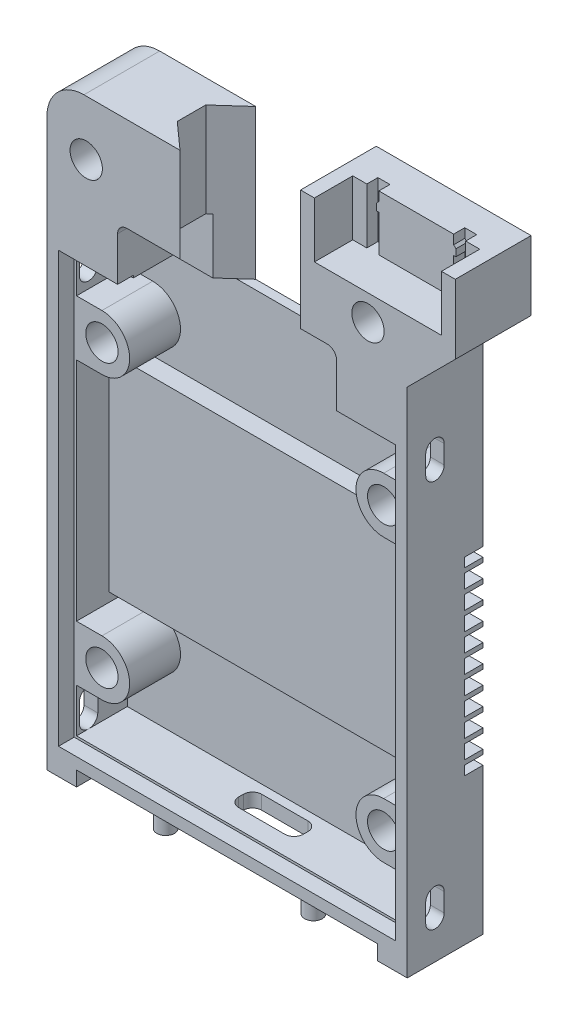
SolidWorks part; units mm, degrees
ref_plane "Front Plane" through (0, 0, 0) normal (0, 0, 1) x (1, 0, 0)
ref_plane "Top Plane" through (0, 0, 0) normal (0, 1, 0) x (1, 0, 0)
ref_plane "Right Plane" through (0, 0, 0) normal (1, 0, 0) x (0, 0, -1)
sketch "Sketch1" plane through (0, 0, 0) normal (0, 0, 1) x (1, 0, 0)
  line L0 (15.25, -20.35) -> (18, -20.35)
  line L1 (-19.5, -32.6) -> (19.5, -32.6)
  line L2 (-19.5, -32.6) -> (-19.5, 31.1)
  line L3 (-19.5, 31.1) -> (19.5, 31.1)
  line L4 (19.5, -32.6) -> (19.5, 31.1)
  line L5 (-15.25, -20.35) -> (-18, -20.35)
  line L6 (15.25, -26.35) -> (18, -26.35)
  line L7 (6.95, 31.1) -> (-15.5, 31.1) construction
  line L8 (-18, -31.1) -> (-18, 29.6)
  line L9 (-18, 29.6) -> (18, 29.6)
  line L10 (18, -31.1) -> (18, 29.6)
  line L11 (-18, -31.1) -> (18, -31.1)
  line L12 (-18, 14.9) -> (18, 14.9)
  line L13 (7.85, 14.9) -> (-4.95, 14.9) construction
  line L14 (-15.25, 4.15) -> (-18, 4.15)
  line L15 (-15.25, 10.15) -> (-18, 10.15)
  line L16 (15.25, 10.15) -> (18, 10.15)
  line L17 (15.25, 4.15) -> (18, 4.15)
  line L18 (-15.25, -26.35) -> (-18, -26.35)
  line L19 (19.5, -34.2) -> (19.5, -18.35) construction
  line L20 (-19.5, -34.2) -> (-19.5, -18.35) construction
  line L21 (15.3, -32.6) -> (-15.3, -32.6) construction
  line L22 (0, 31.1) -> (0, -32.6) construction
  line L23 (9.45, 26.9) -> (24.7, 26.9)
  line L24 (9.45, 26.9) -> (9.45, 33.9)
  line L25 (9.45, 33.9) -> (24.7, 33.9)
  line L26 (24.7, 26.9) -> (24.7, 33.9)
  line L27 (18, 29.6) -> (19.5, 31.1) construction
  line L28 (18.75, 30.35) -> (0, 30.35) construction
  line L29 (9.45, 26.9) -> (7.95, 26.9) construction
  line L30 (-7.95, 31.1) -> (7.95, 31.1)
  line L31 (-7.95, 31.1) -> (-7.95, 29.6)
  line L32 (-7.95, 29.6) -> (7.95, 29.6)
  line L33 (7.95, 31.1) -> (7.95, 29.6)
  line L34 (-7.95, 31.1) -> (7.95, 29.6) construction
  line L35 (-7.95, 29.6) -> (7.95, 31.1) construction
  line L36 (7.95, 26.9) -> (7.95, 29.6) construction
  line L37 (18, 29.6) -> (19.5, 29.6) construction
  line L38 (24.7, 26.4) -> (19.5, 21.2)
  line L39 (9.45, 33.9) -> (7.95, 33.9)
  line L40 (23.2, 33.9) -> (23.2, 26.9)
  line L41 (7.95, 33.9) -> (7.95, 31.1)
  line L42 (24.7, 30.4) -> (23.2, 30.4) construction
  line L43 (24.7, 26.9) -> (19.5, 26.9)
  line L44 (24.7, 26.9) -> (24.7, 26.4)
  line L45 (24.7, 26.4) -> (19.5, 26.4)
  line L46 (19.5, 26.9) -> (19.5, 26.4)
  circle A0 centre (15.25, -23.35) radius 1.75
  arc A1 (-15.5, 31.1) -> (-19.5, 27.1) centre (-15.5, 27.1) ccw construction
  circle A2 centre (15.25, -23.35) radius 3
  arc A3 (-15.5, 31.1) -> (-19.5, 27.1) centre (-15.5, 27.1) ccw
  arc A4 (-15.5, 29.6) -> (-18, 27.1) centre (-15.5, 27.1) ccw
  circle A6 centre (-15.25, -23.35) radius 1.75
  circle A7 centre (-15.25, -23.35) radius 1.75
  circle A8 centre (-15.25, 7.15) radius 1.75
  circle A9 centre (15.25, 7.15) radius 1.75
  circle A10 centre (15.25, 25.15) radius 1.75
  circle A11 centre (-15.25, 25.15) radius 1.75
  circle A12 centre (-15.25, -23.35) radius 3
  circle A13 centre (-15.25, -23.35) radius 3
  circle A14 centre (15.25, 7.15) radius 3
  circle A15 centre (-15.25, 7.15) radius 3
  dimension "D2" = 1.5
  dimension "D4" = 6
  dimension "D3" = 3.5
  dimension "D5" = 13.75
  dimension "D6" = 15.9
  dimension "D7" = 7
  dimension "D8" = 45
  dimension "D9" = 0.5
  dimension "D1" = 1.5
extrude "Base shape" add sketch "Sketch1" along normal up to surface (8.2 mm away) contours A15 L8 L9 L31 L3 A3 L2 L1 L4 L23 L10 A14 A2 L11 A12 | A12 L8 L18 | A12 L8 A6 | L8 A12 | A12 L5 L8 | A15 L8 L14 | A15 L8 A8 | L8 A15 | A15 L15 L8 | L23 A10 L24 L9 A4 L8 L12 L10 A11 | A4 L9 L8 | L33 L3 L31 L9 | L3 L33 L9 L24 | L24 L9 L10 L23 L4 L3 | L24 L23 L10 L9 | A14 L10 L16 | L10 A14 A9 | A14 L17 L10 | L10 A14 | L10 A2 L6 | A2 L10 A0 | L0 A2 L10 | A2 L10 | L40 L25 L24 L3 L4 L23 | L25 L40 L23 L26 | L38 L45 L4 | L45 L44 L23 L4 | L39 L41 L3 L24 region at (16.8481, -20.9099, 0) region at (17.3601, -20.8437, 0) region at (18.7469, -8.1, 0) region at (17.3601, -25.8563, 0) region at (18.1004, -23.35, 0) region at (17.3601, 4.6437, 0) region at (16.8481, 4.7099, 0) region at (18.1004, 7.15, 0) region at (17.3601, 9.6563, 0) region at (-17.3601, -25.8563, 0) region at (-0.6044, 21.831, 0) region at (-18.1004, -23.35, 0) region at (-17.9169, -23.35, 0) region at (13.725, 28.25, 0) region at (15.3803, 29.9053, 0) region at (-17.3601, -20.8437, 0) region at (22.1, 26.65, 0) region at (17.77, 31.4935, 0) region at (-17.3601, 9.6563, 0) region at (-17.4416, 29.0416, 0) region at (8.7, 30.35, 0) region at (21.2333, 24.6667, 0) region at (23.95, 30.4, 0) region at (-16.8481, 9.5901, 0) region at (-18.1004, 7.15, 0) region at (-17.3601, 4.6437, 0) region at (0, 30.35, 0) region at (8.7, 32.5, 0)
sketch "Sketch3" plane through (19.5, 0, 0) normal (1, 0, 0) x (0, 0, -1)
  line L1 (0, -18.35) -> (-2, -18.35)
  line L2 (0, -18.35) -> (0, 2.15)
  line L3 (0, 2.15) -> (-2, 2.15)
  line L4 (-2, -18.35) -> (-2, 2.15)
  line L5 (0, -18.35) -> (1.75, -18.35) construction
  line L6 (0, 2.15) -> (1.75, 2.15) construction
  line L7 (0, -32.6) -> (0, 21.2) construction
  dimension "D1" = 2
extrude "Strap cut" cut sketch "Sketch3" against normal through all
sketch "Sketch4" plane through (0, 31.1, 0) normal (0, 1, 0) x (1, 0, 0)
  line L2 (7.95, 0) -> (-5.0998, 0)
  line L4 (-15.5, 0) -> (7.95, 0) construction
  line L5 (-15.5, -8.2) -> (7.95, -8.2) construction
  line L6 (7.95, -8.2) -> (-5.0998, -8.2)
  line L12 (7.95, -8.3) -> (7.95, 0.1)
  line L13 (7.95, 0.1) -> (-4.9883, 0.1)
  line L14 (-4.9883, 0.1) -> (-7.95, -2.5553)
  line L15 (-7.95, -2.5553) -> (-7.95, -5.6447)
  line L16 (-7.95, -5.6447) -> (-4.9883, -8.3)
  line L17 (-4.9883, -8.3) -> (7.95, -8.3)
  line L18 (7.95, -8.3) -> (7.95, 0.1)
  line L19 (7.95, 0.1) -> (-4.9883, 0.1)
  line L20 (-4.9883, 0.1) -> (-7.95, -2.5553)
  line L21 (-7.95, -2.5553) -> (-7.95, -5.6447)
  line L22 (-7.95, -5.6447) -> (-4.9883, -8.3)
  line L23 (-4.9883, -8.3) -> (7.95, -8.3)
  dimension "D1" = 0.1
extrude "XT60 cut" cut sketch "Sketch4" against normal up to next contours L21 L22 L18 L20 region at (0.4142, 31.1, 4.1)
sketch "Sketch5" plane through (19.5, 0, 0) normal (1, 0, 0) x (0, 0, -1)
  line L1 (-8.2, -32.6) -> (-8.2, 21.2) construction
  line L2 (-6.2, -31.1) -> (-4.2, -31.1)
  line L3 (-6.2, -31.1) -> (-6.2, -27.1)
  line L4 (-6.2, -27.1) -> (-4.2, -27.1)
  line L5 (-4.2, -31.1) -> (-4.2, -27.1)
  line L6 (-8.2, -31.1) -> (0, -31.1) construction
  line L7 (-8.2, 14.9) -> (0, 14.9) construction
  line L8 (-6.2, 14.9) -> (-4.2, 14.9)
  line L9 (-6.2, 14.9) -> (-6.2, 10.9)
  line L10 (-6.2, 10.9) -> (-4.2, 10.9)
  line L11 (-4.2, 14.9) -> (-4.2, 10.9)
  line L14 (-5.2, -27.1) -> (-5.2, -31.1) construction
  line L15 (-5.2, 14.9) -> (-5.2, 10.9) construction
  circle A0 centre (-5.2, -28.1) radius 1
  circle A1 centre (-5.2, -30.1) radius 1
  circle A2 centre (-5.2, 13.9) radius 1
  circle A3 centre (-5.2, 11.9) radius 1
  point P20 (-5.2, -29.1)
  point P31 (-5.2, 12.9)
  dimension "D3" = 4
  dimension "D1" = 2
  dimension "D2" = 2
extrude "Power wires cut" cut sketch "Sketch5" against normal through all contours A2 | A3 | A3 A2 L9 | A3 L11 A2 | A1 | A0 | A1 L5 A0 | A1 A0 L3 region at (19.5, -30.1, 5.2) region at (19.5, -29.1, 5.9766) region at (19.5, -29.1, 4.4234) region at (19.5, -28.1, 5.2) region at (19.5, 13.9, 5.2) region at (19.5, 12.9, 5.9766) region at (19.5, 12.9, 4.4234) region at (19.5, 11.9, 5.2)
sketch "Sketch6" plane through (0, 0, 8.2) normal (0, 0, 1) x (1, 0, 0)
  line L0 (9.15, 14.9) -> (10.85, 14.9) construction
  line L1 (-11.85, 19.9) -> (11.85, 19.9)
  line L2 (-11.85, 19.9) -> (-11.85, 14.9)
  line L3 (-11.85, 14.9) -> (11.85, 14.9)
  line L4 (11.85, 19.9) -> (11.85, 14.9)
  line L5 (-10.85, 20.9) -> (10.85, 20.9)
  arc A0 (11.85, 19.9) -> (10.85, 20.9) centre (10.85, 19.9) ccw construction
  arc A1 (-10.85, 20.9) -> (-11.85, 19.9) centre (-10.85, 19.9) ccw construction
  arc A2 (11.85, 19.9) -> (10.85, 20.9) centre (10.85, 19.9) ccw
  arc A3 (-10.85, 20.9) -> (-11.85, 19.9) centre (-10.85, 19.9) ccw
  line M1 (7.95, 33.9) -> (7.95, 14.9)
  line M15 (-5.0998, 14.9) -> (-5.0998, 31.1)
  line M118 (7.95, 14.9) -> (18, 14.9)
  line M134 (-18, 14.9) -> (-5.0998, 14.9)
extrude "IO wires cut" cut sketch "Sketch6" against normal blind 6 contours L5 A3 L1 M15 | L1 L2 M134 M15 | L5 L1 M15 M1 | L3 L1 M15 M1 | L1 A2 L5 M1 | L4 L1 M1 M118 region at (-8.3714, 20.3909, 8.2) region at (-8.4749, 17.4, 8.2) region at (1.4251, 20.4, 8.2) region at (1.4251, 17.4, 8.2) region at (9.7995, 20.3839, 8.2) region at (9.9, 17.4, 8.2)
sketch "Sketch7" plane through (-18, 0, 0) normal (1, 0, 0) x (0, 0, -1)
  line L6 (0, -18.35) -> (0, -20.35)
  line L7 (-2, -18.35) -> (0, -18.35)
  line L8 (-2, 2.15) -> (-2, -18.35)
  line L9 (0, 2.15) -> (-2, 2.15)
  line L12 (0, 3.15) -> (-3, 3.15)
  line L13 (-3, 3.15) -> (-3, -19.35)
  line L14 (-3, -19.35) -> (-1, -19.35)
  line L15 (-1, -19.35) -> (-1, -20.35)
  line L16 (-1, -20.35) -> (0, -20.35)
  line L17 (0, 3.15) -> (-1, 3.15)
  line L19 (0, -31.1) -> (-1, -31.1)
  line L22 (0, -31.1) -> (0, -20.35)
  line L23 (0, -20.35) -> (-1, -20.35)
  line L24 (-1, -31.1) -> (-1, -20.35)
  line L25 (0, 3.15) -> (0, 14.9)
  line L26 (0, 14.9) -> (-1, 14.9)
  line L27 (-1, 3.15) -> (-1, 14.9)
  line L28 (-5.2, 14.9) -> (0, 14.9) construction
  line L31 (0, -20.35) -> (0, -18.35) construction
  line L32 (0, 2.15) -> (-2, 2.15) construction
  line M48 (0, -20.35) -> (0, -18.35)
  line M49 (0, -18.35) -> (-2, -18.35)
  line M50 (-2, -18.35) -> (-2, 2.15)
  line M51 (-2, 2.15) -> (0, 2.15)
  line M52 (0, 2.15) -> (0, 4.15)
  line M53 (0, 4.15) -> (-8.2, 4.15)
  line M55 (-8.2, -20.35) -> (0, -20.35)
  dimension "D1" = 1
extrude "Bottom" add sketch "Sketch7" along normal up to surface (36 mm away) contours L27 L25 L26 M53 | L27 L12 M52 M53 | L14 L15 L12 L13 M55 M48 M49 M50 M51 M52 | L24 L19 L22 M55 region at (-18, -8.5273, 2.2091) region at (-18, -25.725, 0.5) region at (-18, 3.65, 0.5) region at (-18, 9.525, 0.5) up to face at (18, -8.1, 2.55)
sketch "Sketch9" plane through (0, 0, 0) normal (0, 0, -1) x (-1, 0, 0)
  circle A0 centre (15.25, -23.35) radius 1.75 construction
  circle A1 centre (-15.25, 7.15) radius 1.75 construction
  circle A2 centre (15.25, 7.15) radius 1.75 construction
  circle A3 centre (15.25, -23.35) radius 1.75 construction
  circle A4 centre (15.25, -23.35) radius 1.75
  circle A5 centre (-15.25, 7.15) radius 1.75
  circle A6 centre (15.25, 7.15) radius 1.75
  circle A7 centre (15.25, -23.35) radius 1.75
  circle A8 centre (-15.25, -23.35) radius 1.75 construction
  circle A9 centre (-15.25, -23.35) radius 1.75
extrude "Bottom holes" cut sketch "Sketch9" against normal up to next contours A5 | A6 | A4 | A9 region at (-15.25, -23.35, 0) region at (15.25, 7.15, 0) region at (-15.25, 7.15, 0) region at (15.25, -23.35, 0)
sketch "Sketch8" plane through (0, 0, 8.2) normal (0, 0, 1) x (1, 0, 0)
  line L0 (-6.2152, 14.9) -> (-18, 14.9) construction
  line L1 (-18.25, 15.15) -> (18.25, 15.15)
  line L2 (-18.25, 15.15) -> (-18.25, -31.35)
  line L3 (-18.25, -31.35) -> (18.25, -31.35)
  line L4 (18.25, 15.15) -> (18.25, -31.35)
  line L5 (-18, 14.9) -> (-18.25, 14.9) construction
  line L6 (-18, 14.9) -> (-18, 15.15) construction
  line L7 (18, 14.9) -> (18.25, 14.9) construction
  line L8 (-18, -31.1) -> (-18, -31.35) construction
  dimension "D1" = 0.25
extrude "PCB cut" cut sketch "Sketch8" against normal blind 1.7
sketch "Sketch11" plane through (0, -32.6, 0) normal (0, -1, 0) x (1, 0, 0)
  line L0 (19.5, 8.2) -> (19.5, 0) construction
  line L1 (-19.5, 8.2) -> (19.5, 8.2)
  line L2 (-19.5, 8.2) -> (-19.5, -1.8)
  line L3 (-19.5, -1.8) -> (19.5, -1.8)
  line L4 (19.5, 8.2) -> (19.5, -1.8)
  line L5 (-19.5, 3.2) -> (19.5, 3.2) construction
  line L6 (0, -1.8) -> (0, 8.2) construction
  line L8 (-2.5, 4.45) -> (2.5, 4.45)
  line L9 (-3.5, 3.45) -> (-3.5, 2.95)
  line L10 (-2.5, 1.95) -> (2.5, 1.95)
  line L11 (3.5, 3.45) -> (3.5, 2.95)
  line L12 (-3.5, 4.45) -> (3.5, 1.95) construction
  line L13 (-3.5, 1.95) -> (3.5, 4.45) construction
  arc A0 (2.5, 4.45) -> (3.5, 3.45) centre (2.5, 3.45) cw
  arc A1 (2.5, 1.95) -> (3.5, 2.95) centre (2.5, 2.95) ccw
  arc A2 (-3.5, 2.95) -> (-2.5, 1.95) centre (-2.5, 2.95) ccw
  arc A3 (-2.5, 4.45) -> (-3.5, 3.45) centre (-2.5, 3.45) ccw
  point P11 (0, 3.2)
  dimension "D4" = 1
  dimension "D1" = 10
  dimension "D2" = 7
  dimension "D3" = 2.5
extrude "Ledbar wires cut" cut sketch "Sketch11" against normal up to next contours L8 A3 L9 A2 L10 A1 L11 A0 region at (0, -32.6, 3.2)
sketch "Sketch13" plane through (0, -32.6, 0) normal (0, -1, 0) x (1, 0, 0)
  line L0 (-19.5, 8.2) -> (19.5, 8.2) construction
  line L1 (19.5, 0) -> (16.3, 0)
  line L2 (19.5, 0) -> (19.5, 8.2)
  line L3 (19.5, 8.2) -> (16.3, 8.2)
  line L4 (16.3, 0) -> (16.3, 8.2)
  line L5 (16.1, -1.8) -> (16.1, 8.2) construction
  line L6 (0, 8.2) -> (0, 0) construction
  line L7 (-19.5, 0) -> (-16.3, 0)
  line L8 (-19.5, 0) -> (-19.5, 8.2)
  line L9 (-19.5, 8.2) -> (-16.3, 8.2)
  line L10 (-16.3, 0) -> (-16.3, 8.2)
  dimension "D1" = 0.2
extrude "Ledbar sides" add sketch "Sketch13" along normal blind 1.6
sketch "Sketch14" plane through (0, -32.6, 0) normal (0, -1, 0) x (1, 0, 0)
  circle A0 centre (8, 6.85) radius 0.95
  circle A1 centre (-8, 6.85) radius 0.95
  dimension "D1" = 1.9
extrude "Ledbar mounts" add sketch "Sketch14" along normal blind 2
sketch "Sketch16" plane through (0, 33.9, 0) normal (0, 1, 0) x (1, 0, 0)
  line L0 (7.95, -6.125) -> (24.7, -6.125) construction
  line L1 (7.95, -8.2) -> (24.7, -8.2) construction
  line L2 (21.675, -2.85) -> (20.375, -2.85)
  line L3 (20.375, -4.05) -> (20.375, -2.85)
  line L4 (9.45, -4.05) -> (23.2, -4.05)
  line L5 (9.45, -4.05) -> (9.45, -8.2)
  line L6 (9.45, -8.2) -> (23.2, -8.2)
  line L7 (23.2, -4.05) -> (23.2, -8.2)
  line L8 (9.45, -4.05) -> (23.2, -8.2) construction
  line L9 (9.45, -8.2) -> (23.2, -4.05) construction
  line L10 (24.7, -8.2) -> (24.7, 0) construction
  line L11 (7.95, -8.2) -> (7.95, 0) construction
  line L12 (16.325, -8.2) -> (16.325, -4.05) construction
  line L13 (11.625, -2.85) -> (11.625, -4.05) construction
  line L14 (10.975, -4.05) -> (12.275, -4.05)
  line L15 (10.975, -4.05) -> (10.975, -2.85)
  line L16 (10.975, -2.85) -> (12.275, -2.85)
  line L17 (12.275, -4.05) -> (12.275, -2.85)
  line L18 (10.975, -2.85) -> (10.975, -8.2) construction
  line L19 (21.675, -4.05) -> (21.675, -2.85)
  point P6 (16.325, -6.125)
  dimension "D1" = 13.75
  dimension "D2" = 4.15
  dimension "D3" = 1.3
  dimension "D4" = 1.2
  dimension "D5" = 4.7
extrude "Balance plug cut" cut sketch "Sketch16" against normal blind 6 contours L7 L4 L5 L6 | L4 L17 L16 L15 | L4 L19 L2 L3 region at (21.025, 33.9, 3.45) region at (16.325, 33.9, 6.125) region at (11.625, 33.9, 3.45)
sketch "Sketch17" plane through (0, 0, 2.85) normal (0, 0, 1) x (1, 0, 0)
  line L0 (16.325, 33.9) -> (16.325, 27.9) construction
  line L1 (12.275, 33.9) -> (20.375, 33.9) construction
  line L2 (12.275, 27.9) -> (20.375, 27.9) construction
  line L3 (12.275, 27.9) -> (12.275, 33.9) construction
  line L4 (12.025, 32.9) -> (20.625, 32.9)
  line L5 (12.025, 32.9) -> (12.025, 31.9)
  line L6 (12.025, 31.9) -> (20.625, 31.9)
  line L7 (20.625, 32.9) -> (20.625, 31.9)
  line L8 (12.025, 32.9) -> (20.625, 31.9) construction
  line L9 (12.025, 31.9) -> (20.625, 32.9) construction
  line L10 (12.025, 32.65) -> (12.275, 32.9)
  line L11 (20.625, 32.65) -> (20.375, 32.9)
  point P6 (16.325, 32.4)
  line M7 (20.375, 33.9) -> (20.375, 27.9)
  dimension "D1" = 0.25
  dimension "D2" = 1
  dimension "D3" = 1
  dimension "D4" = 45
extrude "Balance plug locks" add sketch "Sketch17" along normal up to surface (1.2 mm away) contours L10 L5 L6 L4 M7 | L7 L11 L6 M7 region at (16.2154, 32.3984, 2.85) region at (20.494, 32.3405, 2.85) up to face at (16.325, 30.9, 4.05)
sketch "Sketch10" plane through (0, 0, 2) normal (0, 0, -1) x (-1, 0, 0)
  line L0 (0, 2.15) -> (0, -18.35) construction
  line L1 (19.5, 2.15) -> (-19.5, 2.15) construction
  line L2 (19.5, -18.35) -> (-19.5, -18.35) construction
  line L3 (19.5, 2.15) -> (19.5, -18.35) construction
  line L4 (-19.5, 1.15) -> (19.5, 1.15)
  line L5 (-19.5, 1.15) -> (-19.5, 0.65)
  line L6 (-19.5, 0.65) -> (19.5, 0.65)
  line L7 (19.5, 1.15) -> (19.5, 0.65)
  line L8 (-19.5, 1.15) -> (19.5, 0.65) construction
  line L9 (-19.5, 0.65) -> (19.5, 1.15) construction
  line L10 (-19.5, 2.15) -> (19.5, 2.15) construction
  line L11 (-19.5, -1.35) -> (19.5, -1.35)
  line L12 (19.5, -0.85) -> (19.5, -1.35)
  line L13 (-19.5, -0.85) -> (19.5, -0.85)
  line L14 (-19.5, -0.85) -> (-19.5, -1.35)
  line L15 (-19.5, -3.35) -> (19.5, -3.35)
  line L16 (19.5, -2.85) -> (19.5, -3.35)
  line L17 (-19.5, -2.85) -> (19.5, -2.85)
  line L18 (-19.5, -2.85) -> (-19.5, -3.35)
  line L19 (-19.5, -5.35) -> (19.5, -5.35)
  line L20 (19.5, -4.85) -> (19.5, -5.35)
  line L21 (-19.5, -4.85) -> (19.5, -4.85)
  line L22 (-19.5, -4.85) -> (-19.5, -5.35)
  line L23 (-19.5, -7.35) -> (19.5, -7.35)
  line L24 (19.5, -6.85) -> (19.5, -7.35)
  line L25 (-19.5, -6.85) -> (19.5, -6.85)
  line L26 (-19.5, -6.85) -> (-19.5, -7.35)
  line L27 (-19.5, -9.35) -> (19.5, -9.35)
  line L28 (19.5, -8.85) -> (19.5, -9.35)
  line L29 (-19.5, -8.85) -> (19.5, -8.85)
  line L30 (-19.5, -8.85) -> (-19.5, -9.35)
  line L31 (-19.5, -11.35) -> (19.5, -11.35)
  line L32 (19.5, -10.85) -> (19.5, -11.35)
  line L33 (-19.5, -10.85) -> (19.5, -10.85)
  line L34 (-19.5, -10.85) -> (-19.5, -11.35)
  line L35 (-19.5, -13.35) -> (19.5, -13.35)
  line L36 (19.5, -12.85) -> (19.5, -13.35)
  line L37 (-19.5, -12.85) -> (19.5, -12.85)
  line L38 (-19.5, -12.85) -> (-19.5, -13.35)
  line L39 (-19.5, -15.35) -> (19.5, -15.35)
  line L40 (19.5, -14.85) -> (19.5, -15.35)
  line L41 (-19.5, -14.85) -> (19.5, -14.85)
  line L42 (-19.5, -14.85) -> (-19.5, -15.35)
  line L43 (-19.5, -17.35) -> (19.5, -17.35)
  line L44 (19.5, -16.85) -> (19.5, -17.35)
  line L45 (-19.5, -16.85) -> (19.5, -16.85)
  line L46 (-19.5, -16.85) -> (-19.5, -17.35)
  point P6 (0, 0.9)
  dimension "D1" = 1
  dimension "D2" = 0.5
  dimension "D4" = 2
  dimension "D3" = 10
extrude "3D print ribs" add sketch "Sketch10" along normal up to surface (2 mm away) up to face at (-17, 7.15, 0)
sketch "Sketch15" plane through (0, 0, 0) normal (0, 0, -1) x (-1, 0, 0)
  line L0 (-8, -34.6) -> (-8, -32.6) construction
  line L1 (-8.95, -34.6) -> (-7.05, -34.6) construction
  line L2 (-8.95, -32.6) -> (-7.05, -32.6) construction
  line L3 (0, -32.6) -> (0, 14.9) construction
  line L4 (-8.25, -34.6) -> (-7.75, -34.6)
  line L5 (-8.25, -34.6) -> (-8.25, -32.6)
  line L6 (-8.25, -32.6) -> (-7.75, -32.6)
  line L7 (-7.75, -34.6) -> (-7.75, -32.6)
  line L8 (-8.25, -34.6) -> (-7.75, -32.6) construction
  line L9 (-8.25, -32.6) -> (-7.75, -34.6) construction
  line L10 (16.3, -32.6) -> (-16.3, -32.6) construction
  line L11 (-7.95, 14.9) -> (5.0998, 14.9) construction
  line L12 (8.25, -32.6) -> (7.75, -32.6)
  line L13 (7.75, -34.6) -> (7.75, -32.6)
  line L14 (8.25, -34.6) -> (7.75, -34.6)
  line L15 (8.25, -34.6) -> (8.25, -32.6)
  point P6 (-8, -33.6)
  dimension "D1" = 0.5
extrude "3D print led supports" add sketch "Sketch15" against normal up to next
